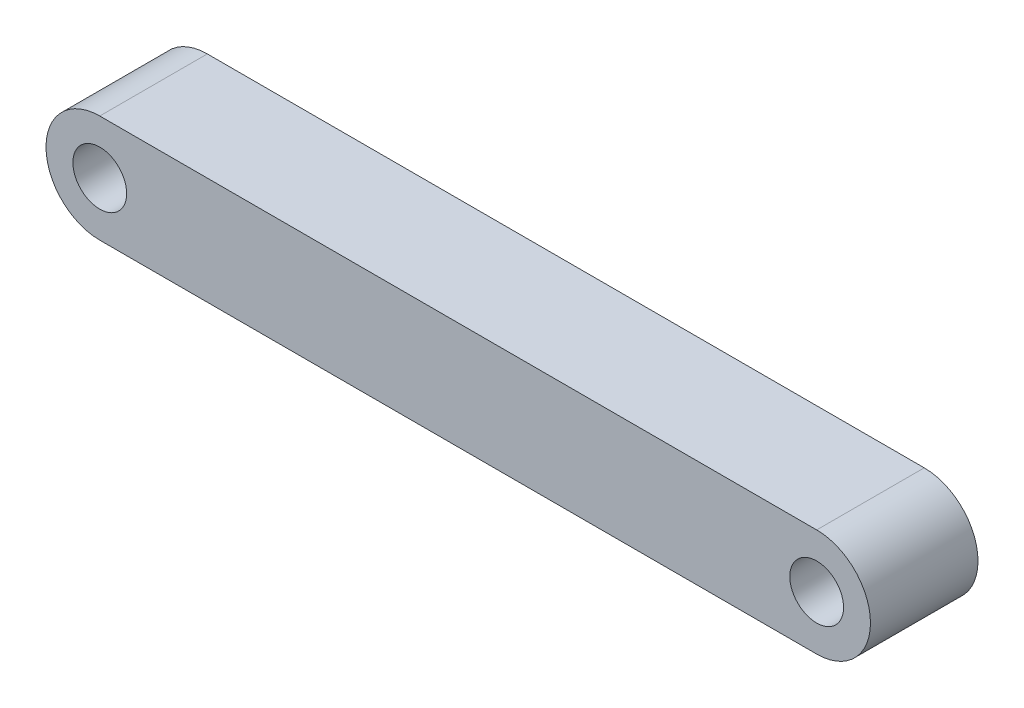
SolidWorks part; units mm, degrees
ref_plane "Plan de face" through (0, 0, 0) normal (0, 0, 1) x (1, 0, 0)
ref_plane "Plan de dessus" through (0, 0, 0) normal (0, 1, 0) x (1, 0, 0)
ref_plane "Plan de droite" through (0, 0, 0) normal (1, 0, 0) x (0, 0, -1)
sketch "Esquisse1" plane through (0, 0, 0) normal (0, 0, 1) x (1, 0, 0)
  line L0 (0, 0) -> (40, 0) construction
  line L1 (0, 3) -> (40, 3)
  line L2 (0, -3) -> (40, -3)
  arc A0 (0, 3) -> (0, -3) centre (0, 0) ccw
  arc A1 (40, -3) -> (40, 3) centre (40, 0) ccw
  circle A2 centre (0, 0) radius 1.5
  circle A3 centre (40, 0) radius 1.5
  point P3 (20, 0)
  dimension "D1" = 3
  dimension "D2" = 6
  dimension "D3" = 40
extrude "Boss.-Extru.1" add sketch "Esquisse1" along normal blind 3 and the other way blind 3
